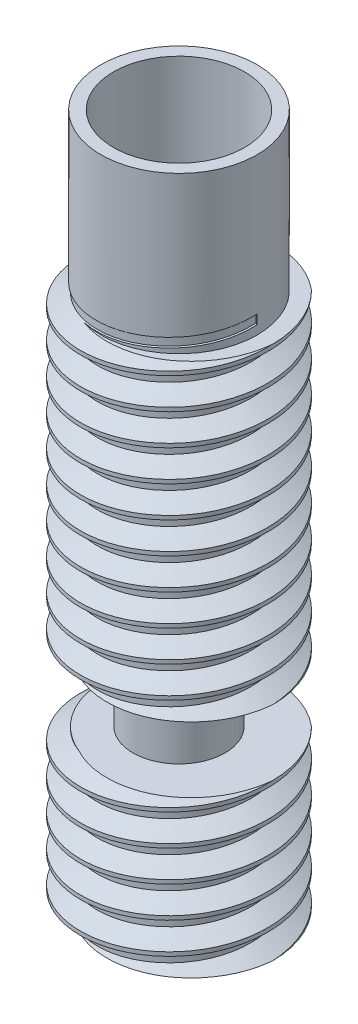
SolidWorks part; units mm, degrees
ref_plane "Alzado" through (0, 0, 0) normal (0, 0, 1) x (1, 0, 0)
ref_plane "Planta" through (0, 0, 0) normal (0, 1, 0) x (1, 0, 0)
ref_plane "Vista lateral" through (0, 0, 0) normal (1, 0, 0) x (0, 0, -1)
sketch "Croquis1" plane through (0, 0, 0) normal (0, 0, 1) x (1, 0, 0)
  line L0 (0, 0) -> (0, 22.1) construction
  line L1 (1, 0) -> (3, 0)
  line L2 (3, 0) -> (3, 5)
  line L3 (3, 5) -> (1.475, 5)
  line L4 (1.475, 5) -> (1.475, 7.1)
  line L5 (1.475, 7.1) -> (3, 7.1)
  line L6 (3, 7.1) -> (3, 17.1)
  line L7 (3, 17.1) -> (2.5, 17.1)
  line L8 (2.5, 17.1) -> (2.5, 22.1)
  line L9 (2.5, 22.1) -> (2.1, 22.1)
  line L10 (2.1, 22.1) -> (2.1, 17.1)
  line L11 (2.1, 17.1) -> (1, 16.9)
  line L12 (1, 16.9) -> (1, 0)
  dimension "D1" = 22.1
  dimension "D2" = 3
  dimension "D3" = 2.1
  dimension "D4" = 5
  dimension "D5" = 22.1
  dimension "D6" = 5
  dimension "D7" = 2.1
  dimension "D8" = 1
  dimension "D9" = 1.475
  dimension "D10" = 3
  dimension "D11" = 0.2
  dimension "D12" = 2.5
revolve "Revolución1" add sketch "Croquis1" angle 360 about L0
thread "Rosca1" pitch 1 method cut profile "Perfil de rosca1" start angle 0, offset 1, length 0, pitch 1, diameter 6
ref_plane "Plano1" through (3, -1, 0) normal (0, 0, 1) x (1, 0, 0)
sketch "Perfil de rosca1" plane through (3, -1, 0) normal (0, 0, 1) x (1, 0, 0)
  line L0 (0, 0) -> (0, 1) construction
  line L11 (0, 0) -> (0, 0.875)
  line L12 (0, 0.875) -> (-0.5413, 0.5625)
  line L13 (-0.5413, 0.5625) -> (-0.5413, 0.3125)
  line L15 (-0.5413, 0.3125) -> (0, 0)
  line L17 (-0.5413, 0.4375) -> (0, 0.4375) construction
  point P2 (0, 0)
  dimension "Pitch" = 1
  dimension "Profile_Angle" = 60
  dimension "Profile_Land" = 0.25
  dimension "Profile_Height" = 0.5413
thread "Rosca2" pitch 1 method cut profile "Perfil de rosca2" start angle 0, offset 1, length 0, pitch 1, diameter 6
ref_plane "Plano2" through (3, 6.1, 0) normal (0, 0, 1) x (1, 0, 0)
sketch "Perfil de rosca2" plane through (3, 6.1, 0) normal (0, 0, 1) x (1, 0, 0)
  line L0 (0, 0) -> (0, 1) construction
  line L11 (0, 0) -> (0, 0.875)
  line L12 (0, 0.875) -> (-0.5413, 0.5625)
  line L13 (-0.5413, 0.5625) -> (-0.5413, 0.3125)
  line L15 (-0.5413, 0.3125) -> (0, 0)
  line L17 (-0.5413, 0.4375) -> (0, 0.4375) construction
  point P2 (0, 0)
  dimension "Pitch" = 1
  dimension "Profile_Angle" = 60
  dimension "Profile_Land" = 0.25
  dimension "Profile_Height" = 0.5413
